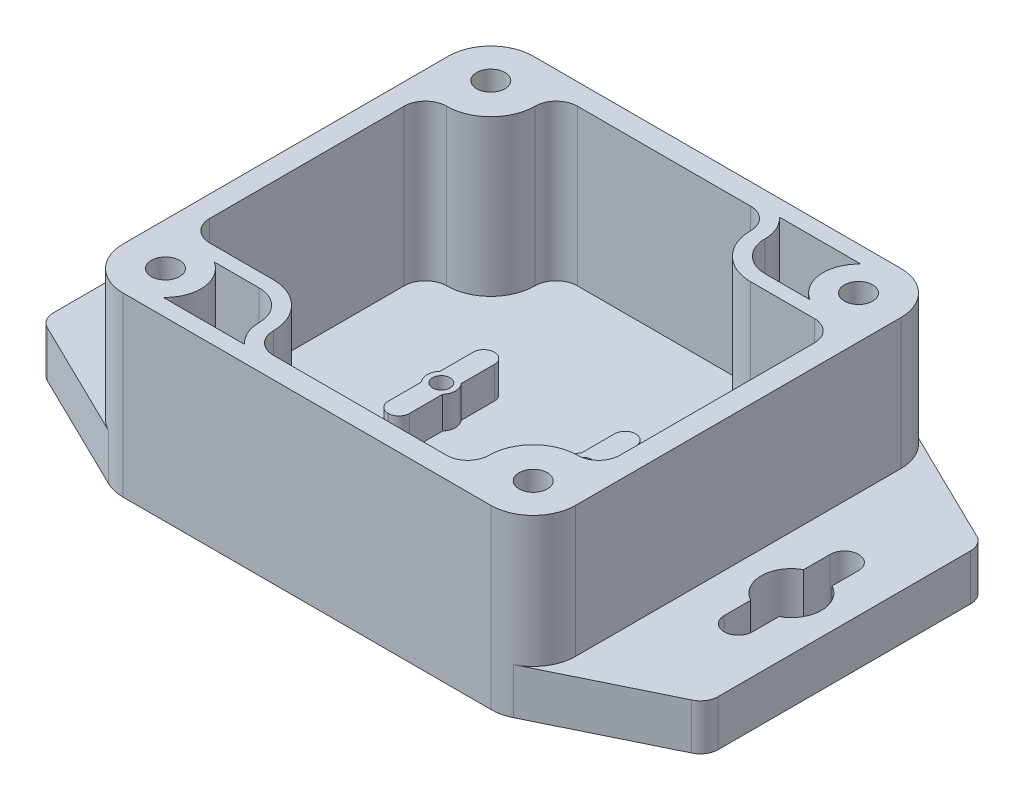
SolidWorks part; units mm, degrees
material "ABS"
ref_plane "Спереди" through (0, 0, 0) normal (0, 0, 1) x (1, 0, 0)
ref_plane "Сверху" through (0, 0, 0) normal (0, 1, 0) x (1, 0, 0)
ref_plane "Справа" through (0, 0, 0) normal (1, 0, 0) x (0, 0, -1)
sketch "Эскиз1" plane through (0, 0, 0) normal (0, 1, 0) x (1, 0, 0)
  line L0 (0, 29) -> (0, -29) construction
  line L1 (-26, 29) -> (26, 29)
  line L2 (-32, 23) -> (-32, -23)
  line L3 (-26, -29) -> (26, -29)
  line L4 (32, 23) -> (32, -23)
  line L5 (-32, 0) -> (32, 0) construction
  line L6 (-11.5, 1.3229) -> (-11.5, 6.01)
  line L7 (-10.01, 7.5) -> (-9.99, 7.5)
  line L8 (-8.5, 6.01) -> (-8.5, 1.3229)
  line L9 (-10, 0) -> (-10, 14.3657) construction
  line L10 (-8.5, -6.01) -> (-8.5, -1.3229)
  line L11 (-11.5, -1.3229) -> (-11.5, -6.01)
  line L12 (8.5, -6.01) -> (8.5, -1.3229)
  line L13 (8.5, 6.01) -> (8.5, 1.3229)
  line L14 (11.5, 1.3229) -> (11.5, 6.01)
  line L15 (11.5, -1.3229) -> (11.5, -6.01)
  line L16 (7.75, 26) -> (-16.75, 26)
  line L17 (-29, 13.75) -> (-29, -13.75)
  line L18 (-7.75, -26) -> (16.75, -26)
  line L19 (29, 13.75) -> (29, -13.75)
  line L20 (-26, 23) -> (-19.75, 23) construction
  line L21 (-26, 23) -> (-26, 16.75) construction
  line L22 (26, 16.75) -> (17, 16.75)
  line L23 (-28.6341, 28.3909) -> (-45.5333, 20.1334)
  line L24 (-26, -16.75) -> (-17, -16.75)
  line L25 (-47, 17.857) -> (-47, -17.857)
  line L26 (-28.6341, -28.3909) -> (-45.5333, -20.1334)
  line L27 (-39.5, 3.6571) -> (-39.5, -4.2355) construction
  line L28 (-41.5, -3.75) -> (-41.5, -7.5)
  line L29 (-41.5, 7.5) -> (-41.5, 3.75)
  line L30 (-37.5, -3.75) -> (-37.5, -7.5)
  line L31 (-37.5, 7.5) -> (-37.5, 3.75)
  line L32 (-48.4914, 0) -> (-42.4166, 0) construction
  line L33 (37.5, -3.75) -> (37.5, -7.5)
  line L34 (41.5, -3.75) -> (41.5, -7.5)
  line L35 (37.5, 7.5) -> (37.5, 3.75)
  line L36 (41.5, 7.5) -> (41.5, 3.75)
  line L37 (28.6341, -28.3909) -> (45.5333, -20.1334)
  line L38 (47, 17.857) -> (47, -17.857)
  line L39 (28.6341, 28.3909) -> (45.5333, 20.1334)
  line L40 (17, 18.75) -> (23.3661, 18.75)
  line L41 (22.637, 26.7) -> (11.113, 26.7)
  line L42 (-9.99, -7.5) -> (-10.01, -7.5)
  line L43 (9.99, 7.5) -> (10.01, 7.5)
  line L44 (-22.637, -26.7) -> (-11.113, -26.7)
  line L45 (-17, -18.75) -> (-23.3661, -18.75)
  line L46 (9.99, -7.5) -> (10.01, -7.5)
  circle A0 centre (-10, 0) radius 1.25
  circle A1 centre (10, 0) radius 1.25
  arc A2 (-11.5, 1.3229) -> (-11.5, -1.3229) centre (-10, 0) ccw
  arc A3 (-9.99, 7.5) -> (-8.5, 6.01) centre (-9.99, 6.01) cw
  arc A4 (-11.5, 6.01) -> (-10.01, 7.5) centre (-10.01, 6.01) cw
  arc A5 (-9.99, -7.5) -> (-8.5, -6.01) centre (-9.99, -6.01) ccw
  arc A6 (-11.5, -6.01) -> (-10.01, -7.5) centre (-10.01, -6.01) ccw
  arc A7 (-8.5, -1.3229) -> (-8.5, 1.3229) centre (-10, 0) ccw
  arc A8 (11.5, -6.01) -> (10.01, -7.5) centre (10.01, -6.01) cw
  arc A9 (9.99, -7.5) -> (8.5, -6.01) centre (9.99, -6.01) cw
  arc A10 (8.5, -1.3229) -> (8.5, 1.3229) centre (10, 0) cw
  arc A11 (9.99, 7.5) -> (8.5, 6.01) centre (9.99, 6.01) ccw
  arc A12 (11.5, 6.01) -> (10.01, 7.5) centre (10.01, 6.01) ccw
  arc A13 (11.5, 1.3229) -> (11.5, -1.3229) centre (10, 0) cw
  circle A14 centre (-26, 23) radius 2
  circle A15 centre (26, 23) radius 2
  circle A16 centre (26, -23) radius 2
  circle A17 centre (-26, -23) radius 2
  arc A18 (-26, 29) -> (-32, 23) centre (-26, 23) ccw
  arc A19 (26, 29) -> (32, 23) centre (26, 23) cw
  arc A20 (26, -29) -> (32, -23) centre (26, -23) ccw
  arc A21 (-26, -29) -> (-32, -23) centre (-26, -23) cw
  arc A22 (-19.75, 23) -> (-26, 16.75) centre (-26, 23) cw
  arc A23 (-16.75, 26) -> (-19.75, 23) centre (-16.75, 23) ccw
  arc A24 (-26, 16.75) -> (-29, 13.75) centre (-26, 13.75) ccw
  arc A25 (19.75, -23) -> (26, -16.75) centre (26, -23) cw
  arc A26 (26, -16.75) -> (29, -13.75) centre (26, -13.75) ccw
  arc A27 (16.75, -26) -> (19.75, -23) centre (16.75, -23) ccw
  arc A28 (10.75, 23) -> (7.75, 26) centre (7.75, 23) ccw
  arc A29 (17, 16.75) -> (10.75, 23) centre (17, 23) cw
  arc A30 (26, 16.75) -> (29, 13.75) centre (26, 13.75) cw
  arc A31 (-26, -16.75) -> (-29, -13.75) centre (-26, -13.75) cw
  arc A32 (-17, -16.75) -> (-10.75, -23) centre (-17, -23) cw
  arc A33 (-47, -17.857) -> (-45.5333, -20.1334) centre (-44.5, -17.857) ccw
  arc A34 (-10.75, -23) -> (-7.75, -26) centre (-7.75, -23) ccw
  arc A35 (-45.5333, 20.1334) -> (-47, 17.857) centre (-44.5, 17.857) ccw
  arc A36 (-37.5, -3.75) -> (-37.5, 3.75) centre (-39.5, 0) ccw
  arc A37 (-37.5, 7.5) -> (-41.5, 7.5) centre (-39.5, 7.5) ccw
  arc A38 (-41.5, 3.75) -> (-41.5, -3.75) centre (-39.5, 0) ccw
  arc A39 (-41.5, -7.5) -> (-37.5, -7.5) centre (-39.5, -7.5) ccw
  arc A40 (41.5, -7.5) -> (37.5, -7.5) centre (39.5, -7.5) cw
  arc A41 (37.5, 7.5) -> (41.5, 7.5) centre (39.5, 7.5) cw
  arc A42 (41.5, 3.75) -> (41.5, -3.75) centre (39.5, 0) cw
  arc A43 (37.5, -3.75) -> (37.5, 3.75) centre (39.5, 0) cw
  arc A44 (47, -17.857) -> (45.5333, -20.1334) centre (44.5, -17.857) cw
  arc A45 (45.5333, 20.1334) -> (47, 17.857) centre (44.5, 17.857) cw
  arc A46 (12.75, 23) -> (17, 18.75) centre (17, 23) ccw
  arc A47 (22.637, 26.7) -> (23.3661, 18.75) centre (26, 23) ccw
  arc A48 (12.75, 23) -> (11.113, 26.7) centre (7.75, 23) ccw
  arc A52 (-22.637, -26.7) -> (-23.3661, -18.75) centre (-26, -23) ccw
  arc A53 (-12.75, -23) -> (-11.113, -26.7) centre (-7.75, -23) ccw
  arc A54 (-12.75, -23) -> (-17, -18.75) centre (-17, -23) ccw
  point P63 (-29, 0)
  point P127 (-30.2426, 27.2426)
  dimension "D4" = 2.5
  dimension "D5" = 4
  dimension "D8" = 1.49
  dimension "D9" = 4
  dimension "D17" = 6
  dimension "D18" = 30.5
  dimension "D16" = 3
  dimension "D14" = 33.5
  dimension "D19" = 33.5
  dimension "D20" = 2.5
  dimension "D15" = 3
  dimension "D22" = 4
  dimension "D21" = 8.5
  dimension "D23" = 94
  dimension "D25" = 15
  dimension "D26" = 3
  dimension "D27" = 2
  dimension "D28" = 2
  dimension "D1" = 64
  dimension "D2" = 58
  dimension "D3" = 20
  dimension "D6" = 7.5
  dimension "D7" = 3
  dimension "D10" = 52
  dimension "D11" = 46
  dimension "D12" = 58
  dimension "D13" = 52
  dimension "D24" = 79
  dimension "D29" = 2
  dimension "D30" = 2.3
  dimension "D31" = 2.3
extrude "Бобышка-Вытянуть1" add sketch "Эскиз1" along normal blind 6.5 contours L23 A35 L25 A33 L26 A21 L2 A18 A39 L28 A38 L29 A37 L31 A36 L30 | A45 L39 A19 L4 A20 L37 A44 L38 L33 A43 L35 A41 L36 A42 L34 A40 region at (-31.5957, 0, -26.4937) region at (36.8217, 0, -23.7259)
extrude "Бобышка-Вытянуть2" add sketch "Эскиз1<3>" along normal blind 25 contours A21 L3 A20 L4 A19 L1 A18 L2 A54 A53 L44 A52 L45 A17 A16 A14 A15 A34 A32 L24 A31 L17 A24 A22 A23 L16 A28 A29 L22 A30 L19 A26 A25 A27 L18 A46 A48 L41 A47 L40 region at (0, 0, -28.1363)
sketch "Эскиз1<3>" plane through (0, 0, 0) normal (0, 1, 0) x (1, 0, 0) same geometry as "Эскиз1"
extrude "Бобышка-Вытянуть3" add sketch "Эскиз1<4>" along normal blind 3 contours A21 L3 A20 L4 A19 L1 A18 L2 A54 A53 L44 A52 L45 A17 A16 A14 A15 A34 A32 L24 A31 L17 A24 A22 A23 L16 A28 A29 L22 A30 L19 A26 A25 A27 L18 A46 A48 L41 A47 L40 | A32 A34 L18 A27 A25 A26 L19 A30 L22 A29 A28 L16 A23 A22 A24 L17 A31 L24 L14 A13 L15 A8 L46 A9 L12 A10 L13 A11 L43 A12 A7 L10 A5 L42 A6 L11 A2 L6 A4 L7 A3 L8 | A53 A54 L45 A52 L44 | A48 A46 L40 A47 L41 | A15 | A14 | A17 | A13 L14 A12 L43 A11 L13 A10 L12 A9 L46 A8 L15 A1 | L10 A7 L8 A3 L7 A4 L6 A2 L11 A6 L42 A5 A0 | A1 | A0 | A16 region at (0, 0, -28.1363) region at (-11.3448, 0, -3.6664) region at (8.6552, 0, 3.6664) region at (0, 0, 0) region at (17.2619, 0, -22.9364) region at (-17.2619, 0, 22.9364) region at (-26, 0, -23) region at (26, 0, -23) region at (-26, 0, 23)
sketch "Эскиз1<4>" plane through (0, 0, 0) normal (0, 1, 0) x (1, 0, 0) same geometry as "Эскиз1"
extrude "Бобышка-Вытянуть8" add sketch "Эскиз1<13>" along normal blind 7.5 contours L8 A7 L10 A5 L42 A6 L11 A2 L6 A4 L7 A3 | L14 A12 L43 A11 L13 A10 L12 A9 L46 A8 L15 A13 | A0 | A1
sketch "Эскиз1<13>" plane through (0, 0, 0) normal (0, 1, 0) x (1, 0, 0) same geometry as "Эскиз1"
extrude "Бобышка-Вытянуть7" add sketch "Эскиз1<12>" along normal blind 7.5 contours L10 A7 L8 A3 L7 A4 L6 A2 L11 A6 L42 A5 A0 | A13 L14 A12 L43 A11 L13 A10 L12 A9 L46 A8 L15 A1 region at (-11.3448, 0, -3.6664) region at (8.6552, 0, 3.6664)
sketch "Эскиз1<12>" plane through (0, 0, 0) normal (0, 1, 0) x (1, 0, 0) same geometry as "Эскиз1"
